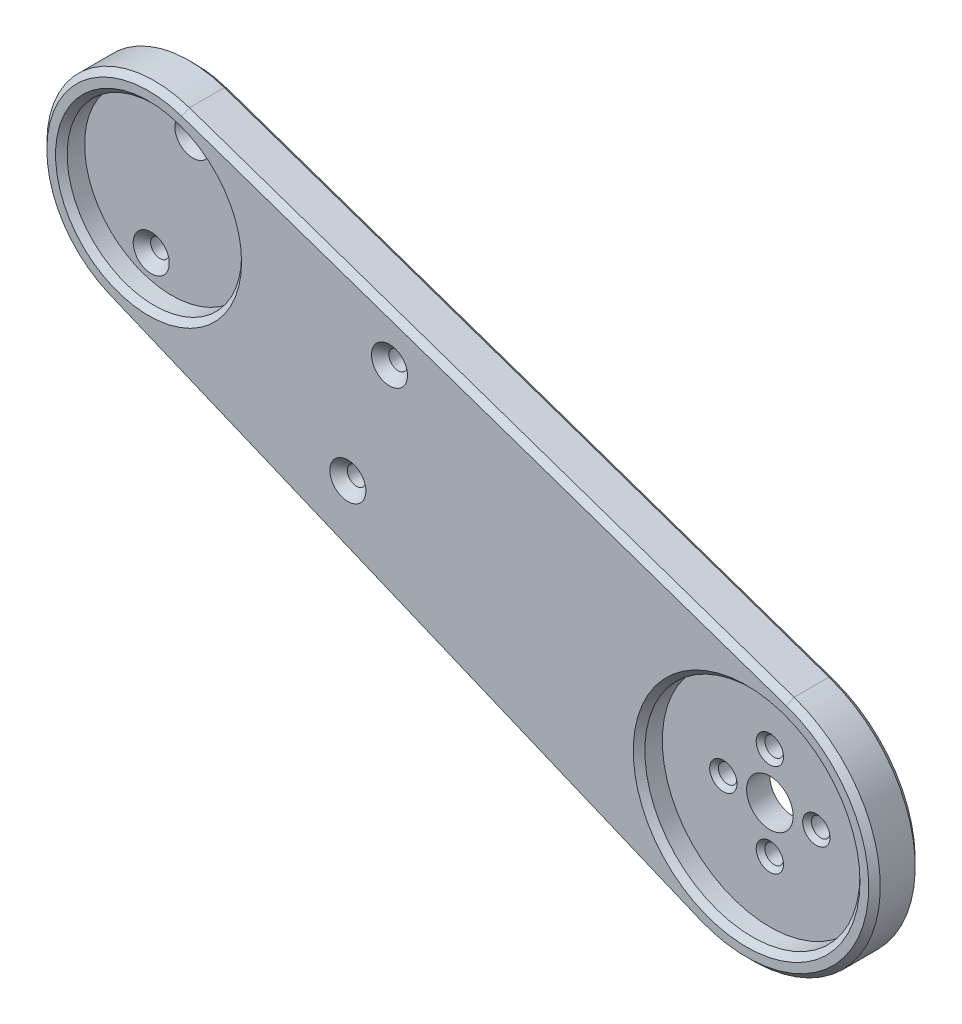
SolidWorks part; units mm, degrees
ref_plane "Front Plane" through (0, 0, 0) normal (0, 0, 1) x (1, 0, 0)
ref_plane "Top Plane" through (0, 0, 0) normal (0, 1, 0) x (1, 0, 0)
ref_plane "Right Plane" through (0, 0, 0) normal (1, 0, 0) x (0, 0, -1)
sketch "Sketch1" plane through (0, 0, 0) normal (0, 0, 1) x (1, 0, 0)
  line L0 (24.7398, -9.308) -> (24.7398, -1.308) construction
  line L1 (24.7398, -9.308) -> (24.7398, -17.308) construction
  line L2 (24.7398, -9.308) -> (32.7398, -9.308) construction
  line L3 (24.7398, -9.308) -> (16.7398, -9.308) construction
  line L4 (-85.2489, 12.7486) -> (16.2679, -29.6113)
  line L5 (-72.1003, 47.3135) -> (31.9039, 11.4929)
  arc A0 (-72.1003, 47.3135) -> (-85.2489, 12.7486) centre (-78.1247, 29.8218) ccw
  arc A1 (16.2679, -29.6113) -> (31.9039, 11.4929) centre (24.7398, -9.308) ccw
  circle A4 centre (24.7398, -1.308) radius 1.6
  circle A5 centre (16.7398, -9.308) radius 1.6
  circle A7 centre (32.7398, -9.308) radius 1.6
  circle A8 centre (24.7398, -17.308) radius 1.6
  circle A9 centre (24.7398, -9.308) radius 22 construction
  circle A10 centre (24.7398, -9.308) radius 18.5
  circle A11 centre (-78.1247, 29.8218) radius 15
  dimension "D1" = 44
  dimension "D2" = 37
  dimension "D3" = 110
  dimension "D4" = 30
  dimension "D6" = 8
  dimension "D9" = 3.2
  dimension "D10" = 37
  dimension "D5" = 8
  dimension "D7" = 8
  dimension "D8" = 8
extrude "Boss-Extrude1" add sketch "Sketch1" along normal blind 8 contours A1 L5 A0 L4 region at (-26.2389, 10.0844, 0)
extrude "Boss-Extrude4" add sketch "Sketch1<5>" along normal blind 4 contours A10 A4 A5 A7 A8 | A11 region at (24.7398, -9.308, 0) region at (-78.1247, 29.8218, 0)
sketch "Sketch1<5>" plane through (0, 0, 0) normal (0, 0, 1) x (1, 0, 0) same geometry as "Sketch1"
chamfer "Chamfer1" distance 0.75 angle 45 4 edges at (18.3398, -9.308, 4) (26.3398, -17.308, 4) (34.3398, -9.308, 4) (26.3398, -1.308, 4)
chamfer "Chamfer3" distance 1 angle 45 2 edges at (43.2398, -9.308, 8) (-63.1247, 29.8218, 8)
sketch "Sketch8" plane through (0, 0, 0) normal (0, 0, -1) x (-1, 0, 0)
  line L0 (-24.7398, -1.308) -> (-24.7398, -17.308) construction
  circle A0 centre (-24.7398, -9.308) radius 4
  dimension "D1" = 8
extrude "Cut-Extrude1" cut sketch "Sketch8" against normal through all
sketch "Sketch10" plane through (0, 0, 0) normal (0, 0, -1) x (-1, 0, 0)
  line L0 (76.3314, 43.9584) -> (85.4168, 17.5791)
  line L4 (76.3314, 43.9584) -> (32.9332, 29.0114)
  line L5 (85.4168, 17.5791) -> (42.0186, 2.6322)
  line L6 (32.9332, 29.0114) -> (42.0186, 2.6322)
  line L7 (72.1003, 47.3135) -> (-31.9039, 11.4929) construction
  line L8 (77.292, 41.1692) -> (74.5028, 40.2085) construction
  line L9 (74.5028, 40.2085) -> (73.5421, 42.9977) construction
  line L10 (54.6323, 36.4849) -> (63.7177, 10.1056) construction
  line L11 (59.175, 23.2953) -> (37.4759, 15.8218) construction
  circle A2 centre (74.5028, 40.2085) radius 1.6
  circle A3 centre (36.6831, 27.1829) radius 1.6
  circle A4 centre (81.6669, 19.4077) radius 1.6
  circle A5 centre (43.8472, 6.382) radius 1.6
  dimension "D4" = 45.9
  dimension "D1" = 27.9
  dimension "D2" = 2.95
  dimension "D3" = 2.95
extrude "Cut-Extrude2" cut sketch "Sketch10" against normal through all both and the other way through all contours A3 | A2 | A4 | A5 region at (-74.5028, 40.2085, 0) region at (-36.6831, 27.1829, 0) region at (-81.6669, 19.4077, 0) region at (-43.8472, 6.382, 0)
chamfer "Chamfer4" distance 1.5 angle 45 4 edges at (-72.9028, 40.2085, 4) (-45.4472, 6.382, 8) (-38.2831, 27.1829, 8) (-80.0669, 19.4077, 4)
chamfer "Chamfer5" distance 1 angle 45 8 edges at (-34.4905, -8.4314, 0) (-95.4159, 36.3994, 0) (45.3023, -17.13, 0) (-20.0982, 29.4032, 0) (-34.4905, -8.4314, 8) (-95.4159, 36.3994, 8) (45.3023, -17.13, 8) (-20.0982, 29.4032, 8)
